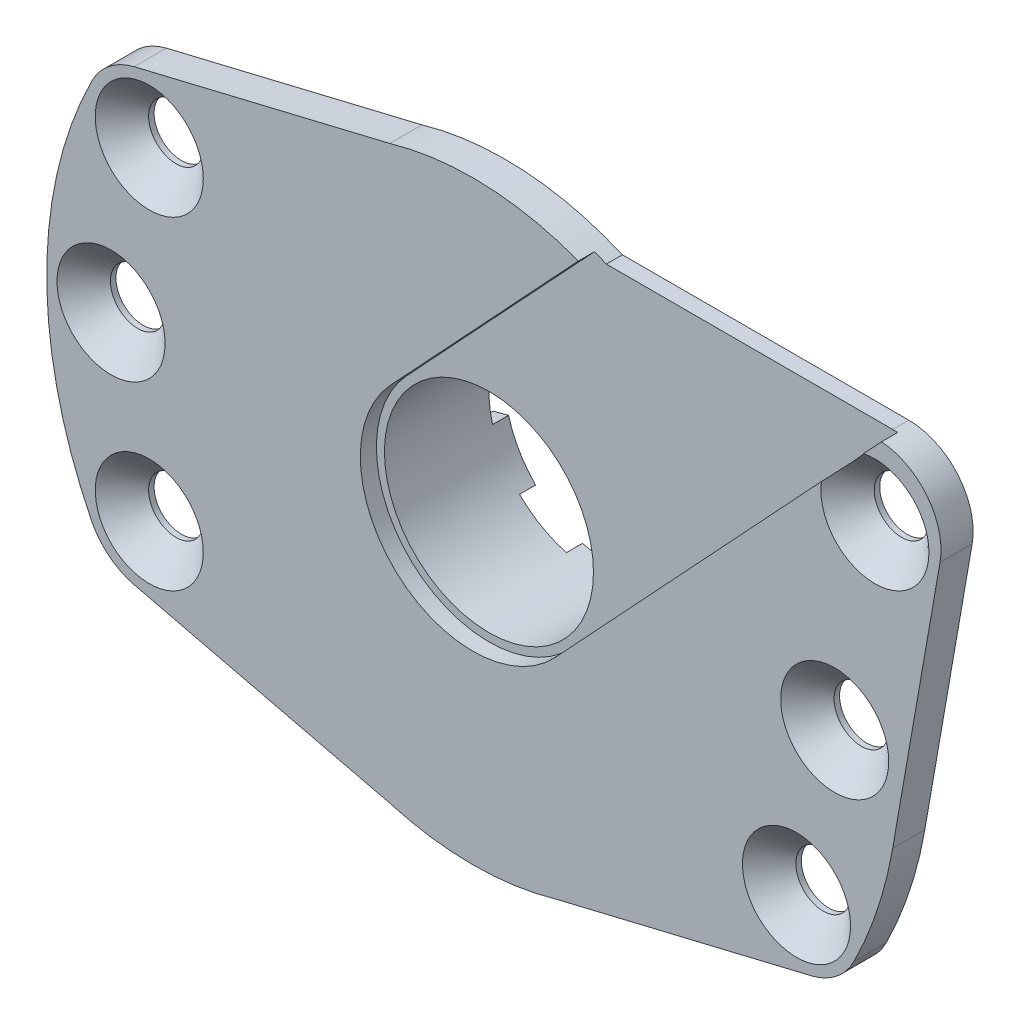
SolidWorks part; units mm, degrees
ref_plane "Спереди" through (0, 0, 0) normal (0, 0, 1) x (1, 0, 0)
ref_plane "Сверху" through (0, 0, 0) normal (0, 1, 0) x (1, 0, 0)
ref_plane "Справа" through (0, 0, 0) normal (1, 0, 0) x (0, 0, -1)
sketch "Эскиз1" plane through (0, 0, 0) normal (0, 0, 1) x (1, 0, 0)
  line L0 (-9.3783, -4.6892) -> (44711.9812, 22355.9906) construction
  line L1 (0, 0.385) -> (0, 50000.385) construction
  line L2 (-11.9154, 0) -> (49988.0846, 0) construction
  line L3 (0, 0) -> (-44721.3595, 22360.6798) construction
  line L4 (-5.1682, 17.7645) -> (-21.0579, 13.9519)
  line L5 (-5.1682, -17.7645) -> (-21.0579, -13.9519)
  line L6 (5.1682, -17.7645) -> (21.0579, -13.9519)
  line L7 (29.0494, 12.3123) -> (26.1054, -4.5561)
  line L8 (25.109, 17) -> (7.3, 17)
  arc A0 (-23.7023, 11.8512) -> (-23.7023, -11.8512) centre (0, 0) ccw
  arc A1 (-23.7023, 11.8512) -> (-21.0579, 13.9519) centre (-20.1246, 10.0623) cw
  arc A2 (7.3, 17) -> (-5.1682, 17.7645) centre (0, 0) ccw
  circle A3 centre (0, 0) radius 22.5 construction
  arc A4 (-23.7023, -11.8512) -> (-21.0579, -13.9519) centre (-20.1246, -10.0623) ccw
  arc A5 (23.7023, -11.8512) -> (21.0579, -13.9519) centre (20.1246, -10.0623) cw
  arc A6 (-5.1682, -17.7645) -> (5.1682, -17.7645) centre (0, 0) ccw
  arc A7 (26.1054, -4.5561) -> (23.7023, -11.8512) centre (0, 0) cw
  circle A9 centre (25, 12.5) radius 0.5
  circle A10 centre (22.5, 0) radius 0.5
  circle A11 centre (20.1246, -10.0623) radius 0.5
  circle A12 centre (-20.1246, -10.0623) radius 0.5
  circle A13 centre (-22.5, 0) radius 0.5
  circle A14 centre (-20.1246, 10.0623) radius 0.5
  circle A15 centre (0, 0) radius 6.5
  arc A16 (25.109, 17) -> (29.0494, 12.3123) centre (25.109, 13) cw
  dimension "D1" = 53
  dimension "D2" = 4
  dimension "D3" = 45
  dimension "D4" = 18.5011
  dimension "D6" = 17
  dimension "D10" = 1
  dimension "D11" = 1
  dimension "D12" = 1
  dimension "D13" = 1
  dimension "D14" = 13
  dimension "D15" = 4
  dimension "D7" = 53.13
  dimension "D8" = 25
  dimension "D9" = 12.5
  dimension "D16" = 99.9
  dimension "D5" = 49.942
extrude "Бобышка-Вытянуть2" add sketch "Эскиз1" along normal blind 2
hole_wizard "Зенковка для винта с потайной головкой и внутренним шестигранником M31" positions "Эскиз2" profile "Эскиз3" countersink size "M3" standard "ISO" end condition through all
sketch "Эскиз2" plane through (0, 0, 2) normal (0, 0, 1) x (1, 0, 0)
  point P0 (-20.1246, 10.0623)
  point P3 (-22.5, 0)
  point P6 (-20.1246, -10.0623)
  point P9 (20.1246, -10.0623)
  point P12 (22.5, 0)
  point P15 (25, 12.5)
sketch "Эскиз3" plane through (-20.1246, 10.0623, 2) normal (1, 0, 0) x (0, -1, 0)
  line L0 (0, 0) -> (0, 2)
  line L1 (0, 2) -> (1.7, 2)
  line L2 (1.7, 2) -> (1.7, 1.66)
  line L3 (1.7, 1.66) -> (3.36, 0)
  line L5 (3.36, 0) -> (0, 0)
  line L6 (-1.7, 1.66) -> (-3.36, 0) construction
  line L11 (0, -6.35) -> (0, 107.95) construction
  dimension "Диаметр сквозного отверстия" = 3.4
  dimension "Глубина сквозного отверстия" = 2
  dimension "Диаметр передней зенковки" = 6.72
  dimension "Угол передней зенковки" = 90
sketch "Эскиз4" plane through (0, 0, 0) normal (0, 0, -1) x (-1, 0, 0)
  circle A0 centre (0, 0) radius 8.5
  circle A1 centre (0, 0) radius 6.5
  dimension "D1" = 17
  dimension "D2" = 13
extrude "Бобышка-Вытянуть3" add sketch "Эскиз4" along normal blind 0.5
sketch "Эскиз5" plane through (0, 0, -0.5) normal (0, 0, -1) x (-1, 0, 0)
  circle A0 centre (0, 0) radius 6.5
  circle A1 centre (0, 0) radius 7.5
  dimension "D1" = 13
  dimension "D2" = 15
extrude "Бобышка-Вытянуть4" add sketch "Эскиз5" along normal blind 5
sketch "Эскиз6" plane through (0, 0, 2) normal (0, 0, 1) x (1, 0, 0)
  line L0 (-5.1195, 4.774) -> (15.3405, 26.7146)
  line L1 (5.1195, -4.774) -> (25.5794, 17.1666)
  line L2 (15.3405, 26.7146) -> (25.5794, 17.1666)
  line L3 (0, 0) -> (50000, 0) construction
  arc A0 (-5.1195, 4.774) -> (5.1195, -4.774) centre (0, 0) ccw
  dimension "D1" = 14
  dimension "D2" = 30
  dimension "D3" = 30
  dimension "D4" = 47
extrude "Вырез-Вытянуть1" cut sketch "Эскиз6" against normal blind 1
sketch "Эскиз7" plane through (0, 0, -5.5) normal (0, 0, -1) x (-1, 0, 0)
  line L0 (0, 0) -> (0, 50000) construction
  line L1 (0, 0) -> (12940.9523, 48296.2913) construction
  line L2 (0, 0) -> (-12940.9523, 48296.2913) construction
  line L3 (-1.9411, 7.2444) -> (-1.6823, 6.2785)
  line L4 (1.9411, 7.2444) -> (1.6823, 6.2785)
  line L5 (5.3033, 5.3033) -> (4.5962, 4.5962)
  line L6 (7.2444, 1.9411) -> (6.2785, 1.6823)
  line L7 (7.2444, -1.9411) -> (6.2785, -1.6823)
  line L8 (5.3033, -5.3033) -> (4.5962, -4.5962)
  line L9 (1.9411, -7.2444) -> (1.6823, -6.2785)
  line L10 (-1.9411, -7.2444) -> (-1.6823, -6.2785)
  line L11 (-5.3033, -5.3033) -> (-4.5962, -4.5962)
  line L12 (-7.2444, -1.9411) -> (-6.2785, -1.6823)
  line L13 (-7.2444, 1.9411) -> (-6.2785, 1.6823)
  line L14 (-5.3033, 5.3033) -> (-4.5962, 4.5962)
  arc A0 (-1.9411, 7.2444) -> (1.9411, 7.2444) centre (0, 0) cw
  arc A2 (-1.6823, 6.2785) -> (1.6823, 6.2785) centre (0, 0) cw
  arc A4 (5.3033, 5.3033) -> (7.2444, 1.9411) centre (0, 0) cw
  arc A5 (4.5962, 4.5962) -> (6.2785, 1.6823) centre (0, 0) cw
  arc A6 (7.2444, -1.9411) -> (5.3033, -5.3033) centre (0, 0) cw
  arc A7 (6.2785, -1.6823) -> (4.5962, -4.5962) centre (0, 0) cw
  arc A8 (1.9411, -7.2444) -> (-1.9411, -7.2444) centre (0, 0) cw
  arc A9 (1.6823, -6.2785) -> (-1.6823, -6.2785) centre (0, 0) cw
  arc A10 (-5.3033, -5.3033) -> (-7.2444, -1.9411) centre (0, 0) cw
  arc A11 (-4.5962, -4.5962) -> (-6.2785, -1.6823) centre (0, 0) cw
  arc A12 (-7.2444, 1.9411) -> (-5.3033, 5.3033) centre (0, 0) cw
  arc A13 (-6.2785, 1.6823) -> (-4.5962, 4.5962) centre (0, 0) cw
  point P35 (0, 0)
  dimension "D3" = 6.5
  dimension "D4" = 7.5
  dimension "D1" = 30
  dimension "D2" = 15
  dimension "D5" = 6
extrude "Бобышка-Вытянуть5" add sketch "Эскиз7" along normal blind 1
